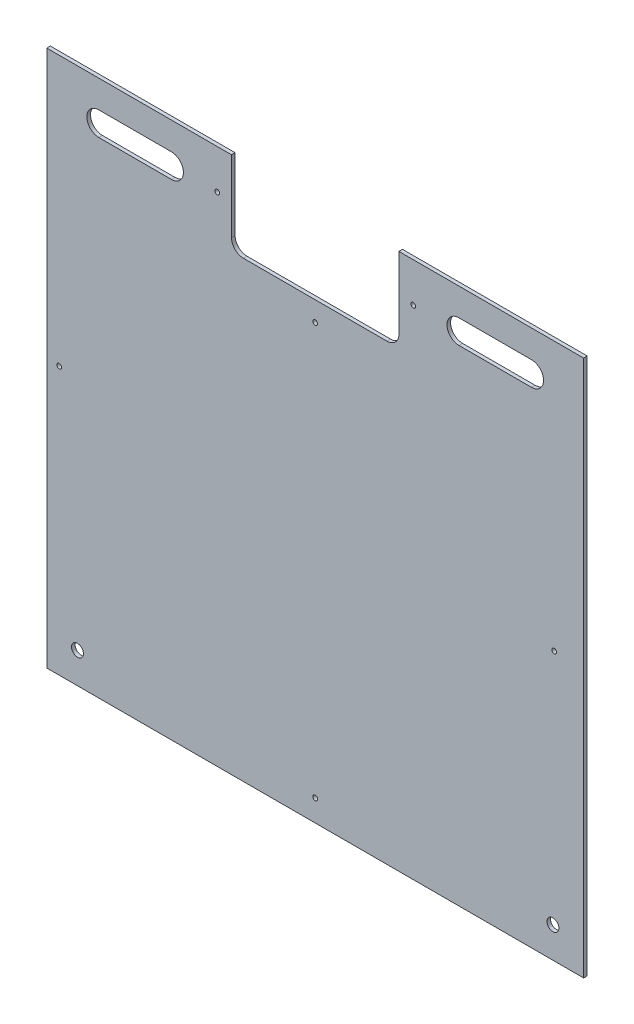
SolidWorks part; units mm, degrees
ref_plane "Piano frontale" through (0, 0, 0) normal (0, 0, 1) x (1, 0, 0)
ref_plane "Piano superiore" through (0, 0, 0) normal (0, 1, 0) x (1, 0, 0)
ref_plane "Piano destro" through (0, 0, 0) normal (1, 0, 0) x (0, 0, -1)
sketch "Schizzo1" plane through (0, 0, 0) normal (0, 0, 1) x (1, 0, 0)
  line L0 (0, 0) -> (0, 449)
  line L1 (0, 449) -> (154.5, 449)
  line L2 (449, 449) -> (449, 0)
  line L3 (449, 0) -> (0, 0)
  line L4 (154.5, 449) -> (154.5, 389)
  line L5 (164.5, 379) -> (284.5, 379)
  line L6 (294.5, 389) -> (294.5, 449)
  line L7 (294.5, 449) -> (449, 449)
  line L8 (154.5, 415.9998) -> (294.5, 415.9998) construction
  line L9 (224.5, 379) -> (224.5, 419) construction
  line L10 (344.7159, 415.9998) -> (405.4404, 415.9998) construction
  line L11 (344.7159, 425.9998) -> (405.4404, 425.9998)
  line L12 (344.7159, 405.9998) -> (405.4404, 405.9998)
  line L13 (104.2841, 415.9998) -> (43.5596, 415.9998) construction
  line L14 (104.2841, 425.9998) -> (43.5596, 425.9998)
  line L15 (104.2841, 405.9998) -> (43.5596, 405.9998)
  line L16 (0, 0) -> (224.5, 224.5) construction
  line L17 (224.5, 224.5) -> (449, 0) construction
  arc A0 (154.5, 389) -> (164.5, 379) centre (164.5, 389) ccw
  arc A1 (294.5, 389) -> (284.5, 379) centre (284.5, 389) cw
  circle A2 centre (142.5666, 415.9998) radius 2
  circle A3 centre (224.5, 362.449) radius 2
  circle A4 centre (306.4334, 415.9998) radius 2
  circle A5 centre (10.4049, 223.8264) radius 2
  circle A6 centre (424.3759, 224.5) radius 2
  circle A7 centre (224.5, 18.1468) radius 2
  arc A8 (344.7159, 425.9998) -> (344.7159, 405.9998) centre (344.7159, 415.9998) ccw
  arc A9 (405.4404, 405.9998) -> (405.4404, 425.9998) centre (405.4404, 415.9998) ccw
  arc A10 (104.2841, 425.9998) -> (104.2841, 405.9998) centre (104.2841, 415.9998) cw
  arc A11 (43.5596, 405.9998) -> (43.5596, 425.9998) centre (43.5596, 415.9998) cw
  circle A12 centre (25.7025, 25.7025) radius 5
  circle A13 centre (423.2975, 25.7025) radius 5
  point P11 (154.5, 379)
  point P14 (294.5, 379)
  point P33 (375.0781, 415.9998)
  point P40 (73.9219, 415.9998)
  dimension "D5" = 10
  dimension "D6" = 4
  dimension "D7" = 4
  dimension "D8" = 4
  dimension "D9" = 4
  dimension "D10" = 4
  dimension "D12" = 10
  dimension "D1" = 449
  dimension "D2" = 449
  dimension "D3" = 140
  dimension "D4" = 70
  dimension "D11" = 20
extrude "Estrusione-Estrusione1" add sketch "Schizzo1" along normal blind 3
